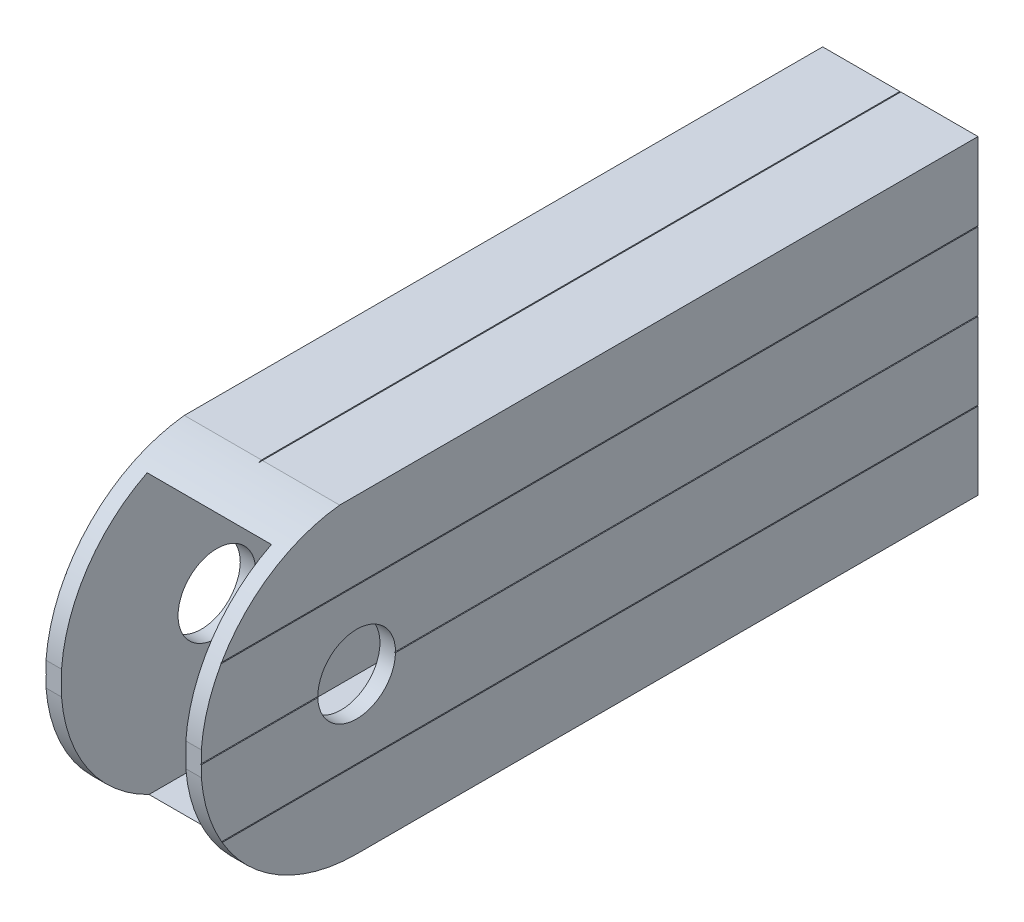
SolidWorks part; units mm, degrees
ref_plane "Front Plane" through (0, 0, 0) normal (0, 0, 1) x (1, 0, 0)
ref_plane "Top Plane" through (0, 0, 0) normal (0, 1, 0) x (1, 0, 0)
ref_plane "Right Plane" through (0, 0, 0) normal (1, 0, 0) x (0, 0, -1)
ref_plane "Plane1" through (12.7, 0, 0) normal (1, 0, 0) x (0, 0, -1)
sketch "Sketch1" plane through (12.7, 0, 0) normal (1, 0, 0) x (0, 0, -1)
  line L0 (-749.3, 25.4) -> (-749.3, -25.4)
  line L1 (-749.3, -25.4) -> (749.3, -25.4)
  line L2 (749.3, -25.4) -> (749.3, 25.4)
  line L3 (749.3, 25.4) -> (-749.3, 25.4)
extrude "Boss-Extrude1" add sketch "Sketch1" against normal blind 25.4
sketch "Sketch2" plane through (0, 0, 749.3) normal (0, 0, 1) x (1, 0, 0)
  line L0 (0.0762, 25.4) -> (-0.0762, 25.4)
  line L1 (-0.0762, 25.4) -> (0.0762, 25.2476)
  line L2 (0.0762, 25.2476) -> (0.0762, 25.4)
extrude "Cut-Extrude1" cut sketch "Sketch2" against normal blind 1498.6
sketch "Sketch3" plane through (0, 0, 749.3) normal (0, 0, 1) x (1, 0, 0)
  line L0 (12.7, 12.6238) -> (12.7, 12.7762)
  line L1 (12.7, 12.7762) -> (12.5476, 12.7762)
  line L2 (12.5476, 12.7762) -> (12.7, 12.6238)
extrude "Cut-Extrude2" cut sketch "Sketch3" against normal through all
sketch "Sketch4" plane through (0, 0, 749.3) normal (0, 0, 1) x (1, 0, 0)
  line L0 (12.7, -0.0762) -> (12.7, 0.0762)
  line L1 (12.7, 0.0762) -> (12.5476, -0.0762)
  line L2 (12.5476, -0.0762) -> (12.7, -0.0762)
extrude "Cut-Extrude3" cut sketch "Sketch4" against normal blind 1498.6
sketch "Sketch5" plane through (0, 0, 749.3) normal (0, 0, 1) x (1, 0, 0)
  line L0 (12.7, -12.7762) -> (12.7, -12.6238)
  line L1 (12.7, -12.6238) -> (12.5476, -12.6238)
  line L2 (12.5476, -12.6238) -> (12.7, -12.7762)
extrude "Cut-Extrude4" cut sketch "Sketch5" against normal blind 1498.6
sketch "Sketch6" plane through (0, 0, 749.3) normal (0, 0, 1) x (1, 0, 0)
  line L0 (0.0762, -25.4) -> (-0.0762, -25.2476)
  line L1 (-0.0762, -25.2476) -> (-0.0762, -25.4)
  line L2 (-0.0762, -25.4) -> (0.0762, -25.4)
extrude "Cut-Extrude5" cut sketch "Sketch6" against normal through all
sketch "Sketch7" plane through (0, 0, 749.3) normal (0, 0, 1) x (1, 0, 0)
  line L0 (-12.7, -12.6238) -> (-12.7, -12.7762)
  line L1 (-12.7, -12.7762) -> (-12.5476, -12.7762)
  line L2 (-12.5476, -12.7762) -> (-12.7, -12.6238)
extrude "Cut-Extrude6" cut sketch "Sketch7" against normal through all
sketch "Sketch8" plane through (0, 0, 749.3) normal (0, 0, 1) x (1, 0, 0)
  line L0 (-12.7, 0.0762) -> (-12.7, -0.0762)
  line L1 (-12.7, -0.0762) -> (-12.5476, 0.0762)
  line L2 (-12.5476, 0.0762) -> (-12.7, 0.0762)
extrude "Cut-Extrude7" cut sketch "Sketch8" against normal blind 1498.6
sketch "Sketch9" plane through (0, 0, 749.3) normal (0, 0, 1) x (1, 0, 0)
  line L0 (-12.7, 12.7762) -> (-12.7, 12.6238)
  line L1 (-12.7, 12.6238) -> (-12.5476, 12.6238)
  line L2 (-12.5476, 12.6238) -> (-12.7, 12.7762)
extrude "Cut-Extrude8" cut sketch "Sketch9" against normal blind 1498.6
sketch "Sketch10" plane through (0, 0, 749.3) normal (0, 0, 1) x (1, 0, 0)
  line L0 (10.16, -22.86) -> (10.16, 22.86)
  line L1 (10.16, 22.86) -> (-10.16, 22.86)
  line L2 (-10.16, 22.86) -> (-10.16, -22.86)
  line L3 (-10.16, -22.86) -> (10.16, -22.86)
extrude "Cut-Extrude9" cut sketch "Sketch10" against normal through all
draft "Draft1" type of draft neutral plane draft angle 45 faces to draft 1 face at (0.0762, 25.3238, 0) neutral plane through (-12.7, 25.4, -749.3) neutral plane normal (0, 1, 0) parameters "D1"=45
draft "Draft2" type of draft neutral plane draft angle 45 faces to draft 1 face at (12.6238, 12.7762, 0) neutral plane through (12.7, 0, 0) neutral plane normal (1, 0, 0) parameters "D1"=45
draft "Draft3" type of draft neutral plane draft angle 45 faces to draft 1 face at (-0.0762, -25.3238, 0) neutral plane through (-12.7, -25.4, 749.3) neutral plane normal (0, -1, 0) parameters "D1"=45
draft "Draft4" type of draft neutral plane draft angle 45 faces to draft 1 face at (-12.6238, -12.7762, 0) neutral plane through (-12.7, 0, 0) neutral plane normal (-1, 0, 0) parameters "D1"=45
draft "Draft5" type of draft neutral plane draft angle 45 faces to draft 2 face at (12.6238, -12.6238, 0) face at (12.6238, 0, 0) neutral plane through (12.7, 0, 0) neutral plane normal (1, 0, 0) parameters "D1"=45
draft "Draft6" type of draft neutral plane draft angle 45 faces to draft 2 face at (-12.6238, 0, 0) face at (-12.6238, 12.6238, 0) neutral plane through (-12.7, 0, 0) neutral plane normal (-1, 0, 0) parameters "D1"=45
sketch "Sketch11" plane through (0, 0, -749.3) normal (0, 0, -1) x (-1, 0, 0)
  line L1 (28.0564, 44.6652) -> (-33.9059, 44.6652)
  line L2 (28.0564, 44.6652) -> (28.0564, -44.0138)
  line L3 (28.0564, -44.0138) -> (-33.9059, -44.0138)
  line L4 (-33.9059, 44.6652) -> (-33.9059, -44.0138)
extrude "Cut-Extrude10" cut sketch "Sketch11" against normal blind 1371.6
sketch "Sketch13" plane through (12.7, 0, 0) normal (1, 0, 0) x (0, 0, -1)
  line L0 (-622.3, 0.0762) -> (-749.3, 0.0762) construction
  line L2 (-749.3, 12.6238) -> (-749.3, 0.0762) construction
  circle A0 centre (-723.9, 0.0762) radius 6.35
  dimension "D1" = 12.7
  dimension "D2" = 25.4
extrude "Cut-Extrude11" cut sketch "Sketch13" against normal blind 25.4
sketch "Sketch14" plane through (12.7, 0, 0) normal (1, 0, 0) x (0, 0, -1)
  line L0 (-749.3, -25.4) -> (-622.3, -25.4) construction
  arc A0 (-723.9, -25.4) -> (-723.9, 25.5524) centre (-723.9, 0.0762) cw
extrude "Cut-Extrude12" cut sketch "Sketch14" against normal blind 25.4 and the other way through all
